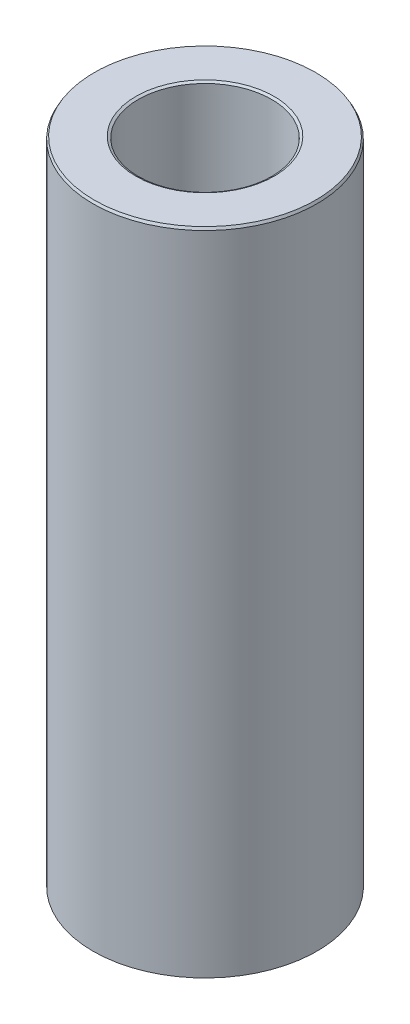
SolidWorks part; units mm, degrees
ref_plane "Front Plane" through (0, 0, 0) normal (0, 0, 1) x (1, 0, 0)
ref_plane "Top Plane" through (0, 0, 0) normal (0, 1, 0) x (1, 0, 0)
ref_plane "Right Plane" through (0, 0, 0) normal (1, 0, 0) x (0, 0, -1)
sketch "Sketch1" plane through (0, 0, 0) normal (0, 1, 0) x (1, 0, 0)
  circle A0 centre (0, 0) radius 57.5
  dimension "SLEEVE_OD" = 115
extrude "Boss-Extrude1" add sketch "Sketch1" along normal blind 334.2008
sketch "Sketch2" plane through (0, 0, 0) normal (0, 1, 0) x (1, 0, 0)
  circle A0 centre (0, 0) radius 34.2488
  dimension "BORE_D" = 68.4976
extrude "Cut-Extrude1" cut sketch "Sketch2" along normal through all
chamfer "Chamfer1" distance 1.2509 angle 30 4 edges at (0, 334.2008, 34.2488) (0, 0, 34.2488) (0, 0, 57.5) (0, 334.2008, 57.5) first distance on face at (0, 334.2008, 34.2488) first distance on face at (0, 0, 34.2488) first distance on face at (0, 334.2008, 57.5)
